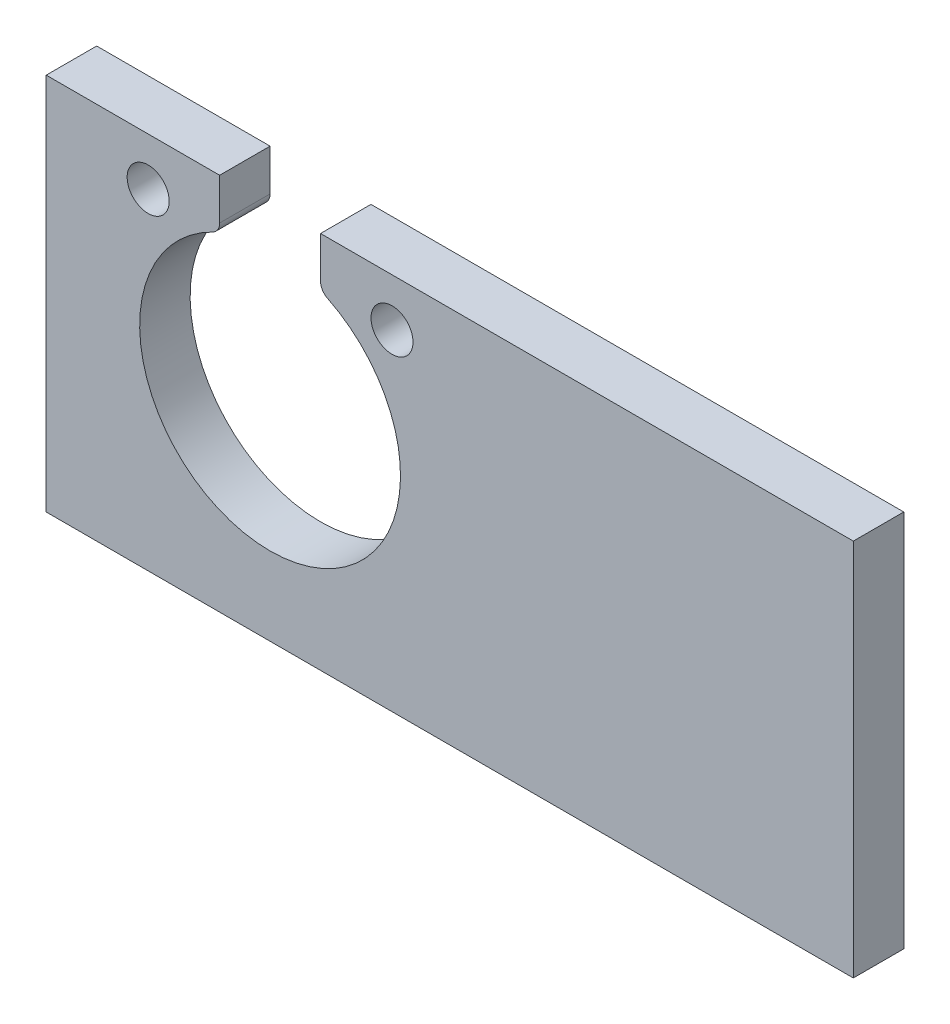
SolidWorks part; units mm, degrees
material "Acrylic (Medium-high impact)"
ref_plane "Front Plane" through (0, 0, 0) normal (0, 0, 1) x (1, 0, 0)
ref_plane "Top Plane" through (0, 0, 0) normal (0, 1, 0) x (1, 0, 0)
ref_plane "Right Plane" through (0, 0, 0) normal (1, 0, 0) x (0, 0, -1)
sketch "Sketch1" plane through (0, 0, 0) normal (0, 0, 1) x (1, 0, 0)
  line L1 (25.1686, 15.8862) -> (-22.8242, 15.8862)
  line L2 (25.1686, 15.8862) -> (25.1686, -6.6138)
  line L3 (25.1686, -6.6138) -> (-22.8242, -6.6138)
  line L4 (-22.8242, 15.8862) -> (-22.8242, -6.6138)
  point P4 (27.1686, 15.8862)
  dimension "D2" = 22.5
extrude "Boss-Extrude1" add sketch "Sketch1" along normal blind 3
sketch "Sketch2" plane through (0, 0, 0) normal (0, 0, -1) x (-1, 0, 0)
  line L9 (6.5138, 15.8862) -> (12.5127, 15.8862)
  line L11 (6.5138, 15.8862) -> (6.5138, 13.4251)
  line L12 (12.5127, 13.4251) -> (12.5127, 15.8862)
  line L13 (6.5138, 15.8862) -> (6.5138, 13.4251)
  line L14 (12.5127, 13.4251) -> (12.5127, 15.8862)
  circle A26 centre (2.2633, 13.0412) radius 1.25
  circle A27 centre (16.7633, 13.0412) radius 1.25
  arc A29 (12.5127, 13.4251) -> (12.9321, 12.7519) centre (13.2627, 13.4251) ccw
  arc A30 (6.0944, 12.7519) -> (6.5138, 13.4251) centre (5.7638, 13.4251) ccw
  arc A31 (6.0944, 12.7519) -> (12.9321, 12.7519) centre (9.5133, 5.7912) ccw
  arc A32 (12.5127, 13.4251) -> (12.9321, 12.7519) centre (13.2627, 13.4251) ccw
  arc A33 (6.0944, 12.7519) -> (6.5138, 13.4251) centre (5.7638, 13.4251) ccw
  arc A34 (6.0944, 12.7519) -> (12.9321, 12.7519) centre (9.5133, 5.7912) ccw
  dimension "D1" = 0.25
extrude "Cut-Extrude1" cut sketch "Sketch2" against normal up to surface (3 mm away) up to face at (1.1722, 4.6362, 3)
